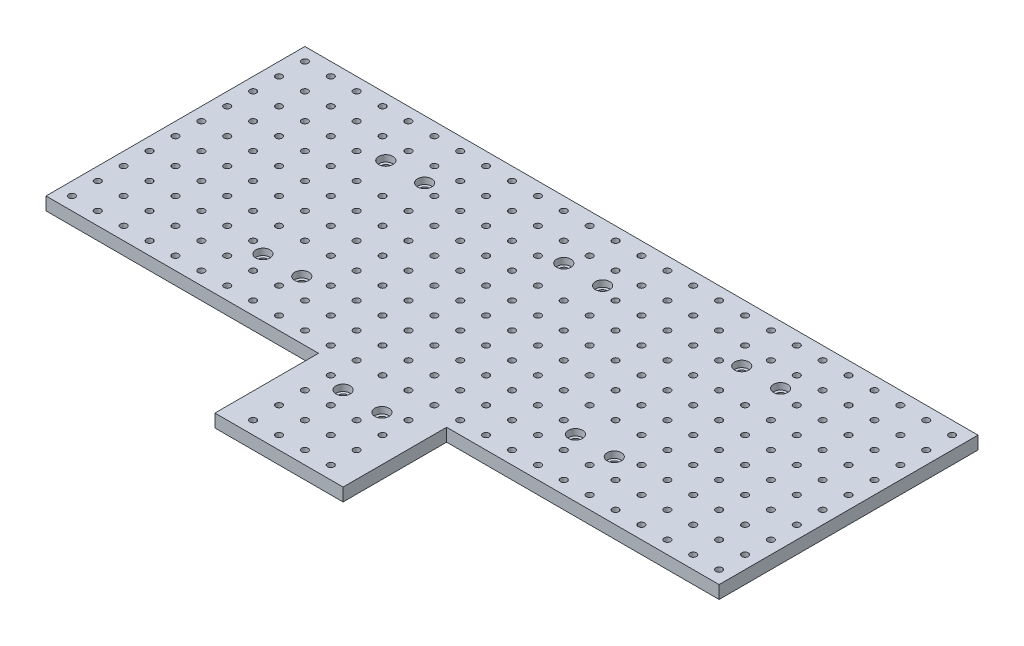
SolidWorks part; units mm, degrees
ref_plane "Front Plane" through (0, 0, 0) normal (0, 0, 1) x (1, 0, 0)
ref_plane "Top Plane" through (0, 0, 0) normal (0, 1, 0) x (1, 0, 0)
ref_plane "Right Plane" through (0, 0, 0) normal (1, 0, 0) x (0, 0, -1)
sketch "Sketch1" plane through (0, 0, 0) normal (0, 1, 0) x (1, 0, 0)
  line L0 (393.065, 0) -> (660.4, 0)
  line L1 (0, 0) -> (267.335, 0)
  line L2 (0, 0) -> (0, 254)
  line L3 (0, 254) -> (660.4, 254)
  line L4 (660.4, 0) -> (660.4, 254)
  line L6 (267.335, 0) -> (267.335, -101.6)
  line L7 (267.335, -101.6) -> (393.065, -101.6)
  line L8 (393.065, 0) -> (393.065, -101.6)
  circle A0 centre (12.7, 241.3) radius 3.175
  circle A1 centre (38.1, 241.3) radius 3.175
  circle A2 centre (63.5, 241.3) radius 3.175
  circle A3 centre (88.9, 241.3) radius 3.175
  circle A4 centre (114.3, 241.3) radius 3.175
  circle A5 centre (139.7, 241.3) radius 3.175
  circle A6 centre (165.1, 241.3) radius 3.175
  circle A7 centre (190.5, 241.3) radius 3.175
  circle A8 centre (215.9, 241.3) radius 3.175
  circle A9 centre (241.3, 241.3) radius 3.175
  circle A10 centre (266.7, 241.3) radius 3.175
  circle A11 centre (292.1, 241.3) radius 3.175
  circle A12 centre (317.5, 241.3) radius 3.175
  circle A13 centre (342.9, 241.3) radius 3.175
  circle A14 centre (368.3, 241.3) radius 3.175
  circle A15 centre (393.7, 241.3) radius 3.175
  circle A16 centre (419.1, 241.3) radius 3.175
  circle A17 centre (444.5, 241.3) radius 3.175
  circle A18 centre (469.9, 241.3) radius 3.175
  circle A19 centre (495.3, 241.3) radius 3.175
  circle A20 centre (520.7, 241.3) radius 3.175
  circle A21 centre (546.1, 241.3) radius 3.175
  circle A22 centre (571.5, 241.3) radius 3.175
  circle A23 centre (596.9, 241.3) radius 3.175
  circle A24 centre (622.3, 241.3) radius 3.175
  circle A25 centre (647.7, 241.3) radius 3.175
  circle A26 centre (38.1, 215.9) radius 3.175
  circle A27 centre (63.5, 215.9) radius 3.175
  circle A28 centre (88.9, 215.9) radius 3.175
  circle A29 centre (114.3, 215.9) radius 3.175
  circle A30 centre (139.7, 215.9) radius 3.175
  circle A31 centre (165.1, 215.9) radius 3.175
  circle A32 centre (190.5, 215.9) radius 3.175
  circle A33 centre (215.9, 215.9) radius 3.175
  circle A34 centre (241.3, 215.9) radius 3.175
  circle A35 centre (266.7, 215.9) radius 3.175
  circle A36 centre (292.1, 215.9) radius 3.175
  circle A37 centre (317.5, 215.9) radius 3.175
  circle A38 centre (342.9, 215.9) radius 3.175
  circle A39 centre (368.3, 215.9) radius 3.175
  circle A40 centre (393.7, 215.9) radius 3.175
  circle A41 centre (419.1, 215.9) radius 3.175
  circle A42 centre (444.5, 215.9) radius 3.175
  circle A43 centre (469.9, 215.9) radius 3.175
  circle A44 centre (495.3, 215.9) radius 3.175
  circle A45 centre (520.7, 215.9) radius 3.175
  circle A46 centre (546.1, 215.9) radius 3.175
  circle A47 centre (571.5, 215.9) radius 3.175
  circle A48 centre (596.9, 215.9) radius 3.175
  circle A49 centre (622.3, 215.9) radius 3.175
  circle A50 centre (647.7, 215.9) radius 3.175
  circle A51 centre (38.1, 190.5) radius 3.175
  circle A52 centre (63.5, 190.5) radius 3.175
  circle A53 centre (88.9, 190.5) radius 3.175
  circle A54 centre (114.3, 190.5) radius 3.175
  circle A57 centre (190.5, 190.5) radius 3.175
  circle A58 centre (215.9, 190.5) radius 3.175
  circle A59 centre (241.3, 190.5) radius 3.175
  circle A60 centre (266.7, 190.5) radius 3.175
  circle A61 centre (292.1, 190.5) radius 3.175
  circle A64 centre (368.3, 190.5) radius 3.175
  circle A65 centre (393.7, 190.5) radius 3.175
  circle A66 centre (419.1, 190.5) radius 3.175
  circle A67 centre (444.5, 190.5) radius 3.175
  circle A68 centre (469.9, 190.5) radius 3.175
  circle A71 centre (546.1, 190.5) radius 3.175
  circle A72 centre (571.5, 190.5) radius 3.175
  circle A73 centre (596.9, 190.5) radius 3.175
  circle A74 centre (622.3, 190.5) radius 3.175
  circle A75 centre (647.7, 190.5) radius 3.175
  circle A76 centre (38.1, 165.1) radius 3.175
  circle A77 centre (63.5, 165.1) radius 3.175
  circle A78 centre (88.9, 165.1) radius 3.175
  circle A79 centre (114.3, 165.1) radius 3.175
  circle A80 centre (139.7, 165.1) radius 3.175
  circle A81 centre (165.1, 165.1) radius 3.175
  circle A82 centre (190.5, 165.1) radius 3.175
  circle A83 centre (215.9, 165.1) radius 3.175
  circle A84 centre (241.3, 165.1) radius 3.175
  circle A85 centre (266.7, 165.1) radius 3.175
  circle A86 centre (292.1, 165.1) radius 3.175
  circle A87 centre (317.5, 165.1) radius 3.175
  circle A88 centre (342.9, 165.1) radius 3.175
  circle A89 centre (368.3, 165.1) radius 3.175
  circle A90 centre (393.7, 165.1) radius 3.175
  circle A91 centre (419.1, 165.1) radius 3.175
  circle A92 centre (444.5, 165.1) radius 3.175
  circle A93 centre (469.9, 165.1) radius 3.175
  circle A94 centre (495.3, 165.1) radius 3.175
  circle A95 centre (520.7, 165.1) radius 3.175
  circle A96 centre (546.1, 165.1) radius 3.175
  circle A97 centre (571.5, 165.1) radius 3.175
  circle A98 centre (596.9, 165.1) radius 3.175
  circle A99 centre (622.3, 165.1) radius 3.175
  circle A100 centre (647.7, 165.1) radius 3.175
  circle A101 centre (38.1, 139.7) radius 3.175
  circle A102 centre (63.5, 139.7) radius 3.175
  circle A103 centre (88.9, 139.7) radius 3.175
  circle A104 centre (114.3, 139.7) radius 3.175
  circle A105 centre (139.7, 139.7) radius 3.175
  circle A106 centre (165.1, 139.7) radius 3.175
  circle A107 centre (190.5, 139.7) radius 3.175
  circle A108 centre (215.9, 139.7) radius 3.175
  circle A109 centre (241.3, 139.7) radius 3.175
  circle A110 centre (266.7, 139.7) radius 3.175
  circle A111 centre (292.1, 139.7) radius 3.175
  circle A112 centre (317.5, 139.7) radius 3.175
  circle A113 centre (342.9, 139.7) radius 3.175
  circle A114 centre (368.3, 139.7) radius 3.175
  circle A115 centre (393.7, 139.7) radius 3.175
  circle A116 centre (419.1, 139.7) radius 3.175
  circle A117 centre (444.5, 139.7) radius 3.175
  circle A118 centre (469.9, 139.7) radius 3.175
  circle A119 centre (495.3, 139.7) radius 3.175
  circle A120 centre (520.7, 139.7) radius 3.175
  circle A121 centre (546.1, 139.7) radius 3.175
  circle A122 centre (571.5, 139.7) radius 3.175
  circle A123 centre (596.9, 139.7) radius 3.175
  circle A124 centre (622.3, 139.7) radius 3.175
  circle A125 centre (647.7, 139.7) radius 3.175
  circle A126 centre (38.1, 114.3) radius 3.175
  circle A127 centre (63.5, 114.3) radius 3.175
  circle A128 centre (88.9, 114.3) radius 3.175
  circle A129 centre (114.3, 114.3) radius 3.175
  circle A130 centre (139.7, 114.3) radius 3.175
  circle A131 centre (165.1, 114.3) radius 3.175
  circle A132 centre (190.5, 114.3) radius 3.175
  circle A133 centre (215.9, 114.3) radius 3.175
  circle A134 centre (241.3, 114.3) radius 3.175
  circle A135 centre (266.7, 114.3) radius 3.175
  circle A136 centre (292.1, 114.3) radius 3.175
  circle A137 centre (317.5, 114.3) radius 3.175
  circle A138 centre (342.9, 114.3) radius 3.175
  circle A139 centre (368.3, 114.3) radius 3.175
  circle A140 centre (393.7, 114.3) radius 3.175
  circle A141 centre (419.1, 114.3) radius 3.175
  circle A142 centre (444.5, 114.3) radius 3.175
  circle A143 centre (469.9, 114.3) radius 3.175
  circle A144 centre (495.3, 114.3) radius 3.175
  circle A145 centre (520.7, 114.3) radius 3.175
  circle A146 centre (546.1, 114.3) radius 3.175
  circle A147 centre (571.5, 114.3) radius 3.175
  circle A148 centre (596.9, 114.3) radius 3.175
  circle A149 centre (622.3, 114.3) radius 3.175
  circle A150 centre (647.7, 114.3) radius 3.175
  circle A151 centre (38.1, 88.9) radius 3.175
  circle A152 centre (63.5, 88.9) radius 3.175
  circle A153 centre (88.9, 88.9) radius 3.175
  circle A154 centre (114.3, 88.9) radius 3.175
  circle A155 centre (139.7, 88.9) radius 3.175
  circle A156 centre (165.1, 88.9) radius 3.175
  circle A157 centre (190.5, 88.9) radius 3.175
  circle A158 centre (215.9, 88.9) radius 3.175
  circle A159 centre (241.3, 88.9) radius 3.175
  circle A160 centre (266.7, 88.9) radius 3.175
  circle A161 centre (292.1, 88.9) radius 3.175
  circle A162 centre (317.5, 88.9) radius 3.175
  circle A163 centre (342.9, 88.9) radius 3.175
  circle A164 centre (368.3, 88.9) radius 3.175
  circle A165 centre (393.7, 88.9) radius 3.175
  circle A166 centre (419.1, 88.9) radius 3.175
  circle A167 centre (444.5, 88.9) radius 3.175
  circle A168 centre (469.9, 88.9) radius 3.175
  circle A169 centre (495.3, 88.9) radius 3.175
  circle A170 centre (520.7, 88.9) radius 3.175
  circle A171 centre (546.1, 88.9) radius 3.175
  circle A172 centre (571.5, 88.9) radius 3.175
  circle A173 centre (596.9, 88.9) radius 3.175
  circle A174 centre (622.3, 88.9) radius 3.175
  circle A175 centre (647.7, 88.9) radius 3.175
  circle A176 centre (38.1, 63.5) radius 3.175
  circle A177 centre (63.5, 63.5) radius 3.175
  circle A178 centre (88.9, 63.5) radius 3.175
  circle A179 centre (114.3, 63.5) radius 3.175
  circle A180 centre (139.7, 63.5) radius 3.175
  circle A183 centre (215.9, 63.5) radius 3.175
  circle A184 centre (241.3, 63.5) radius 3.175
  circle A185 centre (266.7, 63.5) radius 3.175
  circle A186 centre (292.1, 63.5) radius 3.175
  circle A187 centre (317.5, 63.5) radius 3.175
  circle A188 centre (342.9, 63.5) radius 3.175
  circle A189 centre (368.3, 63.5) radius 3.175
  circle A190 centre (393.7, 63.5) radius 3.175
  circle A191 centre (419.1, 63.5) radius 3.175
  circle A192 centre (444.5, 63.5) radius 3.175
  circle A195 centre (520.7, 63.5) radius 3.175
  circle A196 centre (546.1, 63.5) radius 3.175
  circle A197 centre (571.5, 63.5) radius 3.175
  circle A198 centre (596.9, 63.5) radius 3.175
  circle A199 centre (622.3, 63.5) radius 3.175
  circle A200 centre (647.7, 63.5) radius 3.175
  circle A201 centre (38.1, 38.1) radius 3.175
  circle A202 centre (63.5, 38.1) radius 3.175
  circle A203 centre (88.9, 38.1) radius 3.175
  circle A204 centre (114.3, 38.1) radius 3.175
  circle A205 centre (139.7, 38.1) radius 3.175
  circle A206 centre (165.1, 38.1) radius 3.175
  circle A207 centre (190.5, 38.1) radius 3.175
  circle A208 centre (215.9, 38.1) radius 3.175
  circle A209 centre (241.3, 38.1) radius 3.175
  circle A210 centre (266.7, 38.1) radius 3.175
  circle A211 centre (292.1, 38.1) radius 3.175
  circle A212 centre (317.5, 38.1) radius 3.175
  circle A213 centre (342.9, 38.1) radius 3.175
  circle A214 centre (368.3, 38.1) radius 3.175
  circle A215 centre (393.7, 38.1) radius 3.175
  circle A216 centre (419.1, 38.1) radius 3.175
  circle A217 centre (444.5, 38.1) radius 3.175
  circle A218 centre (469.9, 38.1) radius 3.175
  circle A219 centre (495.3, 38.1) radius 3.175
  circle A220 centre (520.7, 38.1) radius 3.175
  circle A221 centre (546.1, 38.1) radius 3.175
  circle A222 centre (571.5, 38.1) radius 3.175
  circle A223 centre (596.9, 38.1) radius 3.175
  circle A224 centre (622.3, 38.1) radius 3.175
  circle A225 centre (647.7, 38.1) radius 3.175
  circle A226 centre (38.1, 12.7) radius 3.175
  circle A227 centre (63.5, 12.7) radius 3.175
  circle A228 centre (88.9, 12.7) radius 3.175
  circle A229 centre (114.3, 12.7) radius 3.175
  circle A230 centre (139.7, 12.7) radius 3.175
  circle A231 centre (165.1, 12.7) radius 3.175
  circle A232 centre (190.5, 12.7) radius 3.175
  circle A233 centre (215.9, 12.7) radius 3.175
  circle A234 centre (241.3, 12.7) radius 3.175
  circle A235 centre (266.7, 12.7) radius 3.175
  circle A236 centre (292.1, 12.7) radius 3.175
  circle A237 centre (317.5, 12.7) radius 3.175
  circle A238 centre (342.9, 12.7) radius 3.175
  circle A239 centre (368.3, 12.7) radius 3.175
  circle A240 centre (393.7, 12.7) radius 3.175
  circle A241 centre (419.1, 12.7) radius 3.175
  circle A242 centre (444.5, 12.7) radius 3.175
  circle A243 centre (469.9, 12.7) radius 3.175
  circle A244 centre (495.3, 12.7) radius 3.175
  circle A245 centre (520.7, 12.7) radius 3.175
  circle A246 centre (546.1, 12.7) radius 3.175
  circle A247 centre (571.5, 12.7) radius 3.175
  circle A248 centre (596.9, 12.7) radius 3.175
  circle A249 centre (622.3, 12.7) radius 3.175
  circle A250 centre (647.7, 12.7) radius 3.175
  circle A261 centre (292.1, -12.7) radius 3.175
  circle A264 centre (368.3, -12.7) radius 3.175
  circle A286 centre (292.1, -38.1) radius 3.175
  circle A287 centre (317.5, -38.1) radius 3.175
  circle A288 centre (342.9, -38.1) radius 3.175
  circle A289 centre (368.3, -38.1) radius 3.175
  circle A311 centre (292.1, -63.5) radius 3.175
  circle A312 centre (317.5, -63.5) radius 3.175
  circle A313 centre (342.9, -63.5) radius 3.175
  circle A314 centre (368.3, -63.5) radius 3.175
  circle A336 centre (292.1, -88.9) radius 3.175
  circle A337 centre (317.5, -88.9) radius 3.175
  circle A338 centre (342.9, -88.9) radius 3.175
  circle A339 centre (368.3, -88.9) radius 3.175
  circle A351 centre (12.7, 215.9) radius 3.175
  circle A352 centre (12.7, 190.5) radius 3.175
  circle A353 centre (12.7, 165.1) radius 3.175
  circle A354 centre (12.7, 139.7) radius 3.175
  circle A355 centre (12.7, 114.3) radius 3.175
  circle A356 centre (12.7, 88.9) radius 3.175
  circle A357 centre (12.7, 63.5) radius 3.175
  circle A358 centre (12.7, 38.1) radius 3.175
  circle A359 centre (12.7, 12.7) radius 3.175
  circle A364 centre (38.1, -12.7) radius 3.175 [skipped]
  circle A365 centre (12.7, -12.7) radius 3.175 [skipped]
  circle A366 centre (63.5, -12.7) radius 3.175 [skipped]
  circle A367 centre (88.9, -12.7) radius 3.175 [skipped]
  circle A368 centre (114.3, -12.7) radius 3.175 [skipped]
  circle A369 centre (190.5, -12.7) radius 3.175 [skipped]
  circle A370 centre (215.9, -12.7) radius 3.175 [skipped]
  circle A371 centre (241.3, -12.7) radius 3.175 [skipped]
  circle A372 centre (165.1, -12.7) radius 3.175 [skipped]
  circle A373 centre (139.7, -12.7) radius 3.175 [skipped]
  circle A374 centre (38.1, -38.1) radius 3.175 [skipped]
  circle A375 centre (12.7, -38.1) radius 3.175 [skipped]
  circle A376 centre (63.5, -38.1) radius 3.175 [skipped]
  circle A377 centre (88.9, -38.1) radius 3.175 [skipped]
  circle A378 centre (114.3, -38.1) radius 3.175 [skipped]
  circle A379 centre (139.7, -38.1) radius 3.175 [skipped]
  circle A380 centre (165.1, -38.1) radius 3.175 [skipped]
  circle A381 centre (190.5, -38.1) radius 3.175 [skipped]
  circle A382 centre (215.9, -38.1) radius 3.175 [skipped]
  circle A383 centre (241.3, -38.1) radius 3.175 [skipped]
  circle A384 centre (241.3, -63.5) radius 3.175 [skipped]
  circle A385 centre (241.3, -88.9) radius 3.175 [skipped]
  circle A386 centre (215.9, -63.5) radius 3.175 [skipped]
  circle A387 centre (215.9, -88.9) radius 3.175 [skipped]
  circle A388 centre (190.5, -88.9) radius 3.175 [skipped]
  circle A389 centre (190.5, -63.5) radius 3.175 [skipped]
  circle A390 centre (165.1, -63.5) radius 3.175 [skipped]
  circle A391 centre (139.7, -63.5) radius 3.175 [skipped]
  circle A392 centre (139.7, -88.9) radius 3.175 [skipped]
  circle A393 centre (114.3, -88.9) radius 3.175 [skipped]
  circle A394 centre (12.7, -88.9) radius 3.175 [skipped]
  circle A395 centre (38.1, -88.9) radius 3.175 [skipped]
  circle A396 centre (63.5, -88.9) radius 3.175 [skipped]
  circle A397 centre (88.9, -88.9) radius 3.175 [skipped]
  circle A398 centre (114.3, -63.5) radius 3.175 [skipped]
  circle A399 centre (88.9, -63.5) radius 3.175 [skipped]
  circle A400 centre (63.5, -63.5) radius 3.175 [skipped]
  circle A401 centre (38.1, -63.5) radius 3.175 [skipped]
  circle A402 centre (12.7, -63.5) radius 3.175 [skipped]
  circle A403 centre (165.1, -88.9) radius 3.175 [skipped]
  circle A404 centre (647.7, -12.7) radius 3.175 [skipped]
  circle A405 centre (647.7, -38.1) radius 3.175 [skipped]
  circle A406 centre (647.7, -63.5) radius 3.175 [skipped]
  circle A407 centre (647.7, -88.9) radius 3.175 [skipped]
  circle A408 centre (622.3, -88.9) radius 3.175 [skipped]
  circle A409 centre (622.3, -63.5) radius 3.175 [skipped]
  circle A410 centre (622.3, -38.1) radius 3.175 [skipped]
  circle A411 centre (622.3, -12.7) radius 3.175 [skipped]
  circle A412 centre (596.9, -12.7) radius 3.175 [skipped]
  circle A413 centre (596.9, -38.1) radius 3.175 [skipped]
  circle A414 centre (596.9, -63.5) radius 3.175 [skipped]
  circle A415 centre (596.9, -88.9) radius 3.175 [skipped]
  circle A416 centre (571.5, -88.9) radius 3.175 [skipped]
  circle A417 centre (571.5, -38.1) radius 3.175 [skipped]
  circle A418 centre (571.5, -12.7) radius 3.175 [skipped]
  circle A419 centre (546.1, -12.7) radius 3.175 [skipped]
  circle A420 centre (546.1, -38.1) radius 3.175 [skipped]
  circle A421 centre (546.1, -63.5) radius 3.175 [skipped]
  circle A422 centre (546.1, -88.9) radius 3.175 [skipped]
  circle A423 centre (571.5, -63.5) radius 3.175 [skipped]
  circle A424 centre (520.7, -88.9) radius 3.175 [skipped]
  circle A425 centre (495.3, -88.9) radius 3.175 [skipped]
  circle A426 centre (444.5, -88.9) radius 3.175 [skipped]
  circle A427 centre (419.1, -88.9) radius 3.175 [skipped]
  circle A428 centre (419.1, -63.5) radius 3.175 [skipped]
  circle A429 centre (419.1, -38.1) radius 3.175 [skipped]
  circle A430 centre (419.1, -12.7) radius 3.175 [skipped]
  circle A431 centre (469.9, -12.7) radius 3.175 [skipped]
  circle A432 centre (520.7, -12.7) radius 3.175 [skipped]
  circle A433 centre (520.7, -38.1) radius 3.175 [skipped]
  circle A434 centre (520.7, -63.5) radius 3.175 [skipped]
  circle A435 centre (495.3, -63.5) radius 3.175 [skipped]
  circle A436 centre (444.5, -63.5) radius 3.175 [skipped]
  circle A437 centre (469.9, -63.5) radius 3.175 [skipped]
  circle A438 centre (469.9, -88.9) radius 3.175 [skipped]
  circle A439 centre (495.3, -38.1) radius 3.175 [skipped]
  circle A440 centre (495.3, -12.7) radius 3.175 [skipped]
  circle A441 centre (469.9, -38.1) radius 3.175 [skipped]
  circle A442 centre (444.5, -12.7) radius 3.175 [skipped]
  circle A443 centre (444.5, -38.1) radius 3.175 [skipped]
  arc A444 (267.335, -15.8109) -> (267.335, -9.5891) centre (266.7, -12.7) ccw [skipped]
  arc A445 (267.335, -41.2109) -> (267.335, -34.9891) centre (266.7, -38.1) ccw [skipped]
  arc A446 (267.335, -66.6109) -> (267.335, -60.3891) centre (266.7, -63.5) ccw [skipped]
  arc A447 (267.335, -92.0109) -> (267.335, -85.7891) centre (266.7, -88.9) ccw [skipped]
  arc A448 (393.065, -9.5891) -> (393.065, -15.8109) centre (393.7, -12.7) ccw [skipped]
  arc A449 (393.065, -34.9891) -> (393.065, -41.2109) centre (393.7, -38.1) ccw [skipped]
  arc A450 (393.065, -85.7891) -> (393.065, -92.0109) centre (393.7, -88.9) ccw [skipped]
  arc A451 (393.065, -60.3891) -> (393.065, -66.6109) centre (393.7, -63.5) ccw [skipped]
  circle A452 centre (139.7, 190.5) radius 3.175 [skipped]
  circle A453 centre (165.1, 190.5) radius 3.175 [skipped]
  circle A454 centre (317.5, 190.5) radius 3.175 [skipped]
  circle A455 centre (342.9, 190.5) radius 3.175 [skipped]
  circle A456 centre (520.7, 190.5) radius 3.175 [skipped]
  circle A457 centre (495.3, 190.5) radius 3.175 [skipped]
  circle A458 centre (165.1, 63.5) radius 3.175 [skipped]
  circle A459 centre (190.5, 63.5) radius 3.175 [skipped]
  circle A460 centre (469.9, 63.5) radius 3.175 [skipped]
  circle A461 centre (495.3, 63.5) radius 3.175 [skipped]
  circle A462 centre (342.9, -12.7) radius 3.175 [skipped]
  circle A463 centre (317.5, -12.7) radius 3.175 [skipped]
  dimension "D6" = 6.35
  dimension "D1" = 254
  dimension "D2" = 660.4
  dimension "D3" = 125.73
  dimension "D4" = 267.335
  dimension "D5" = 101.6
  dimension "D7" = 12.7
  dimension "D8" = 12.7
  dimension "D9" = 26
  dimension "D10" = 14
extrude "Boss-Extrude1" add sketch "Sketch1" along normal blind 12.7
sketch "Sketch2" plane through (0, 12.7, 0) normal (0, 1, 0) x (1, 0, 0)
  line L0 (660.4, 254) -> (0, 254) construction
  line L1 (0, 254) -> (0, 0) construction
  line L2 (660.4, 0) -> (660.4, 254) construction
  line L3 (393.065, 0) -> (660.4, 0) construction
  line L4 (393.065, -101.6) -> (393.065, 0) construction
  circle A0 centre (136.525, 196.85) radius 4.191
  circle A1 centre (136.525, 196.85) radius 6.985
  circle A2 centre (174.625, 196.85) radius 4.191
  circle A3 centre (174.625, 196.85) radius 6.985
  circle A4 centre (311.15, 196.85) radius 4.191
  circle A5 centre (311.15, 196.85) radius 6.985
  circle A6 centre (349.25, 196.85) radius 4.191
  circle A7 centre (349.25, 196.85) radius 6.985
  circle A8 centre (485.775, 196.85) radius 4.191
  circle A9 centre (485.775, 196.85) radius 6.985
  circle A10 centre (523.875, 196.85) radius 4.191
  circle A11 centre (523.875, 196.85) radius 6.985
  circle A12 centre (310.515, -19.05) radius 4.191
  circle A13 centre (310.515, -19.05) radius 6.985
  circle A14 centre (348.615, -19.05) radius 4.191
  circle A15 centre (348.615, -19.05) radius 6.985
  circle A16 centre (155.6777, 57.15) radius 4.191
  circle A17 centre (155.6777, 57.15) radius 6.985
  circle A18 centre (193.7777, 57.15) radius 4.191
  circle A19 centre (193.7777, 57.15) radius 6.985
  circle A20 centre (462.2911, 57.15) radius 4.191
  circle A21 centre (462.2911, 57.15) radius 6.985
  circle A22 centre (500.3911, 57.15) radius 4.191
  circle A23 centre (500.3911, 57.15) radius 6.985
  dimension "D1" = 8.382
  dimension "D2" = 13.97
  dimension "D10" = 8.382
  dimension "D11" = 13.97
  dimension "D3" = 38.1
  dimension "D4" = 38.1
  dimension "D5" = 38.1
  dimension "D6" = 57.15
  dimension "D7" = 136.525
  dimension "D8" = 136.525
  dimension "D9" = 136.525
  dimension "D12" = 38.1
  dimension "D13" = 38.1
  dimension "D14" = 38.1
  dimension "D15" = 19.05
  dimension "D16" = 44.45
  dimension "D17" = 57.15
extrude "Cut-Extrude1" cut sketch "Sketch2" against normal blind 6.35
extrude "Cut-Extrude2" cut sketch "Sketch2<2>" against normal offset from surface (25.4 mm away) 25.4 contours A0 | A2 | A4 | A6 | A8 | A10 region at (136.525, 12.7, -196.85) region at (174.625, 12.7, -196.85) region at (311.15, 12.7, -196.85) region at (349.25, 12.7, -196.85) region at (485.775, 12.7, -196.85) region at (523.875, 12.7, -196.85) up to face at (136.525, 12.7, -189.865)
sketch "Sketch2<2>" plane through (0, 12.7, 0) normal (0, 1, 0) x (1, 0, 0) same geometry as "Sketch2"
extrude "Cut-Extrude3" cut sketch "Sketch2<3>" against normal offset from surface (25.4 mm away) 25.4 contours A16 | A18 | A20 | A22 | A14 | A12 up to face at (136.525, 12.7, -189.865)
sketch "Sketch2<3>" plane through (0, 12.7, 0) normal (0, 1, 0) x (1, 0, 0) same geometry as "Sketch2"
